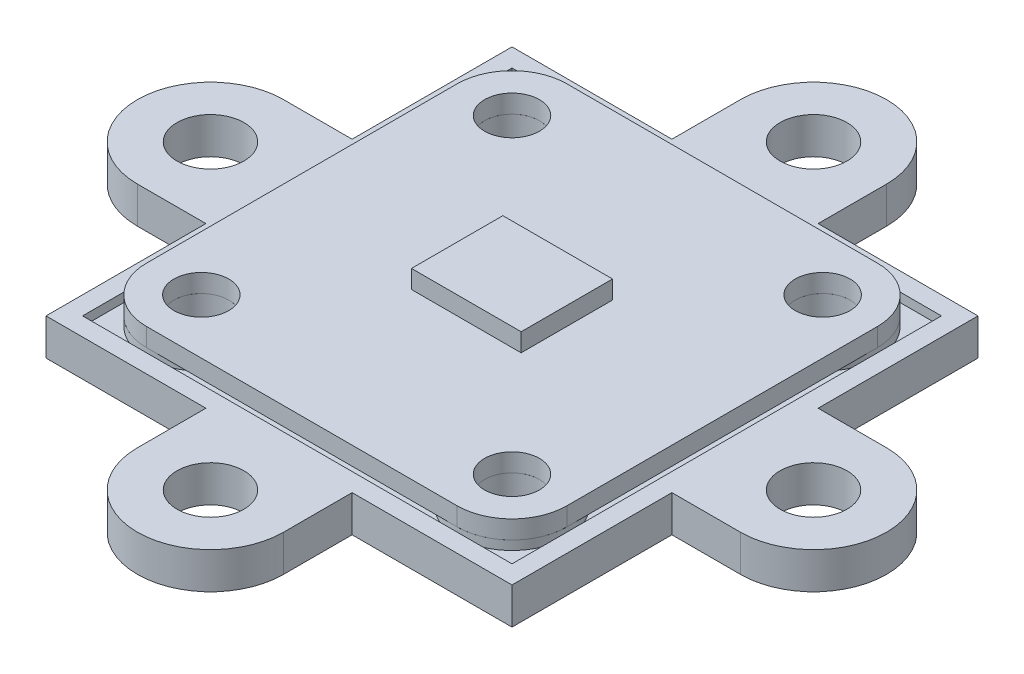
SolidWorks part; units mm, degrees
ref_plane "Front Plane" through (0, 0, 0) normal (0, 0, 1) x (1, 0, 0)
ref_plane "Top Plane" through (0, 0, 0) normal (0, 1, 0) x (1, 0, 0)
ref_plane "Right Plane" through (0, 0, 0) normal (1, 0, 0) x (0, 0, -1)
other "Bounding Box"
ref_plane "Default Plane" through (-8.9266, -12.7485, 0) normal (-0.1736, 0.9848, 0) x (0.9848, 0.1736, 0)
sketch "Sketch1" plane through (0, 0, 0) normal (0, 1, 0) x (1, 0, 0)
  line L1 (-11.5, -11.5) -> (11.5, -11.5)
  line L2 (-11.5, -11.5) -> (-11.5, 11.5)
  line L3 (-11.5, 11.5) -> (11.5, 11.5)
  line L4 (11.5, -11.5) -> (11.5, 11.5)
  line L5 (-11.5, -11.5) -> (11.5, 11.5) construction
  line L6 (-11.5, 11.5) -> (11.5, -11.5) construction
  line L7 (-8.5, 8.5) -> (8.5, 8.5) construction
  line L8 (-8.5, 8.5) -> (-8.5, -8.5) construction
  line L9 (-8.5, -8.5) -> (8.5, -8.5) construction
  line L10 (8.5, 8.5) -> (8.5, -8.5) construction
  line L11 (-8.5, 8.5) -> (8.5, -8.5) construction
  line L12 (-8.5, -8.5) -> (8.5, 8.5) construction
  circle A0 centre (-8.5, 8.5) radius 1.5
  circle A1 centre (8.5, 8.5) radius 1.5
  circle A2 centre (8.5, -8.5) radius 1.5
  circle A3 centre (-8.5, -8.5) radius 1.5
  point P0 (0, 0)
  point P6 (0, 0)
  dimension "D3" = 3
  dimension "D1" = 17
  dimension "D2" = 23
extrude "Boss-Extrude1" add sketch "Sketch1" along normal blind 1
sketch "Sketch2" plane through (0, 1, 0) normal (0, 1, 0) x (1, 0, 0)
  line L1 (-3, 2.5) -> (3, 2.5)
  line L2 (-3, 2.5) -> (-3, -2.5)
  line L3 (-3, -2.5) -> (3, -2.5)
  line L4 (3, 2.5) -> (3, -2.5)
  line L5 (-3, 2.5) -> (3, -2.5) construction
  line L6 (-3, -2.5) -> (3, 2.5) construction
  point P0 (0, 0)
  dimension "D1" = 5
  dimension "D2" = 6
extrude "Boss-Extrude2" add sketch "Sketch2" along normal blind 1
fillet "Fillet1" radius 3 4 edges at (-11.5, 0.5, -11.5) (11.5, 0.5, -11.5) (11.5, 0.5, 11.5) (-11.5, 0.5, 11.5)
sketch "Sketch3" plane through (0, 1, 0) normal (0, 1, 0) x (1, 0, 0)
  line L0 (-11.5, 8.5) -> (-11.5, -8.5) construction
  line L1 (-11.75, 11.75) -> (11.75, 11.75) construction
  line L2 (-11.75, 11.75) -> (-11.75, -11.75) construction
  line L3 (-11.75, -11.75) -> (11.75, -11.75) construction
  line L4 (11.75, 11.75) -> (11.75, -11.75) construction
  line L5 (-11.75, 11.75) -> (11.75, -11.75) construction
  line L6 (-11.75, -11.75) -> (11.75, 11.75) construction
  line L8 (-12.75, 12.75) -> (12.75, 12.75)
  line L9 (-12.75, 12.75) -> (-12.75, -12.75)
  line L10 (-12.75, -12.75) -> (12.75, -12.75)
  line L11 (12.75, 12.75) -> (12.75, -12.75)
  line L12 (-12.75, 12.75) -> (12.75, -12.75) construction
  line L13 (-12.75, -12.75) -> (12.75, 12.75) construction
  circle A0 centre (-8.5, 8.5) radius 1.5 construction
  circle A1 centre (8.5, 8.5) radius 1.5 construction
  circle A2 centre (8.5, -8.5) radius 1.5 construction
  circle A3 centre (-8.5, -8.5) radius 1.5 construction
  circle A4 centre (-8.5, 8.5) radius 1.5
  circle A5 centre (8.5, 8.5) radius 1.5
  circle A6 centre (8.5, -8.5) radius 1.5
  circle A7 centre (-8.5, -8.5) radius 1.5
  circle A8 centre (0, 0) radius 7.5
  point P12 (0, 0)
  point P20 (0, 0)
  dimension "D3" = 15
  dimension "D1" = 0.25
  dimension "D2" = 1
extrude "Boss-Extrude3" add sketch "Sketch3" along normal blind 1.5 from offset 3 separate body offset against normal yes
sketch "Sketch4" plane through (0, -2, 0) normal (0, -1, 0) x (1, 0, 0)
  circle A0 centre (-8.5, 8.5) radius 3
  circle A1 centre (-8.5, -8.5) radius 1.5
  circle A2 centre (-8.5, -8.5) radius 1.5
  circle A3 centre (8.5, -8.5) radius 1.5
  circle A4 centre (8.5, -8.5) radius 1.5
  circle A5 centre (8.5, 8.5) radius 1.5
  circle A6 centre (8.5, 8.5) radius 1.5
  circle A7 centre (-8.5, 8.5) radius 1.5
  circle A8 centre (-8.5, 8.5) radius 1.5
  circle A9 centre (8.5, 8.5) radius 3
  circle A10 centre (8.5, -8.5) radius 3
  circle A11 centre (-8.5, -8.5) radius 3
  arc A12 (-8.5, 11.5) -> (-11.5, 8.5) centre (-8.5, 8.5) ccw construction
  dimension "D1" = 0
  dimension "D2" = 0
  dimension "D3" = 0
  dimension "D4" = 0
extrude "Boss-Extrude4" add sketch "Sketch4" against normal up to surface (2 mm away) up to face at (8.5, 0, 10)
sketch "Sketch5" plane through (0, -2, 0) normal (0, -1, 0) x (1, 0, 0)
  line L0 (11.75, -11.75) -> (11.75, 11.75) construction
  line L1 (-11.75, 11.75) -> (11.75, 11.75) construction
  line L2 (-11.75, -11.75) -> (-11.75, 11.75) construction
  line L3 (-11.75, -11.75) -> (11.75, -11.75) construction
  line L4 (-12.75, -12.75) -> (12.75, -12.75) construction
  line L5 (12.75, -12.75) -> (12.75, 12.75) construction
  line L6 (-12.75, 12.75) -> (12.75, 12.75) construction
  line L7 (-12.75, -12.75) -> (-12.75, 12.75) construction
  line L8 (11.75, -11.75) -> (11.75, 11.75)
  line L9 (-11.75, 11.75) -> (11.75, 11.75)
  line L10 (-11.75, -11.75) -> (-11.75, 11.75)
  line L11 (-11.75, -11.75) -> (11.75, -11.75)
  line L12 (-12.75, -12.75) -> (12.75, -12.75)
  line L13 (12.75, -12.75) -> (12.75, 12.75)
  line L14 (-12.75, 12.75) -> (12.75, 12.75)
  line L15 (-12.75, -12.75) -> (-12.75, 12.75)
extrude "Boss-Extrude5" add sketch "Sketch5" against normal blind 2
sketch "Sketch6" plane through (0, 0, 0) normal (0, 1, 0) x (-1, 0, 0)
  line L0 (0, -16.5) -> (0, 0) construction
  line L1 (-4, -16.5) -> (-4, -12.75)
  line L2 (12.75, -12.75) -> (-12.75, -12.75) construction
  line L3 (-4, -12.75) -> (4, -12.75)
  line L4 (4, -12.75) -> (4, -16.5)
  circle A0 centre (0, -16.5) radius 1.8288
  arc A1 (-4, -16.5) -> (4, -16.5) centre (0, -16.5) ccw
  dimension "D2" = 3.6576
  dimension "D3" = 4
  dimension "D1" = 16.5
extrude "Boss-Extrude6" add sketch "Sketch6" against normal blind 2
ref_axis "Axis1" through (0, -0.175, 0) along (0, 1, 0)
pattern_circular "CirPattern1" count 4 over 360 about axis through (0, -0.175, 0) along (0, 1, 0) of "Boss-Extrude6"
